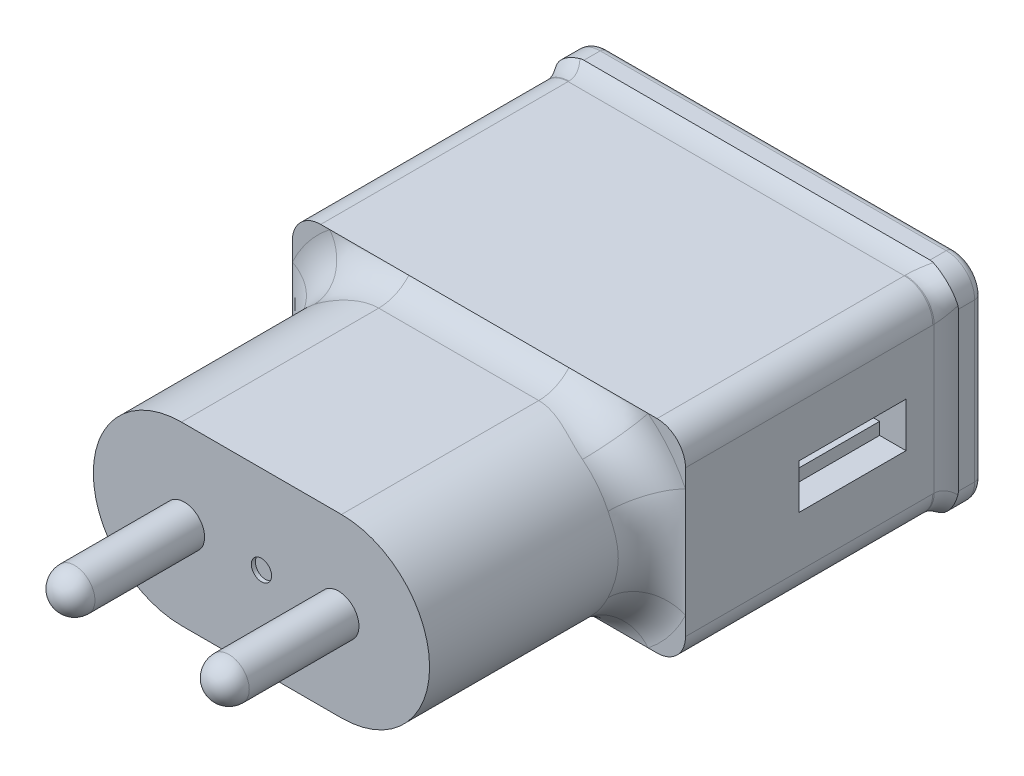
SolidWorks part; units mm, degrees
ref_plane "Front Plane" through (0, 0, 0) normal (0, 0, 1) x (1, 0, 0)
ref_plane "Top Plane" through (0, 0, 0) normal (0, 1, 0) x (1, 0, 0)
ref_plane "Right Plane" through (0, 0, 0) normal (1, 0, 0) x (0, 0, -1)
sketch "Sketch1" plane through (0, 0, 0) normal (0, 0, 1) x (1, 0, 0)
  line L0 (-9.85, 0) -> (9.85, 0) construction
  line L1 (-9.85, 10.85) -> (9.85, 10.85)
  line L2 (-9.85, -10.85) -> (9.85, -10.85)
  arc A0 (-9.85, 10.85) -> (-9.85, -10.85) centre (-9.85, 0) ccw
  arc A1 (9.85, -10.85) -> (9.85, 10.85) centre (9.85, 0) ccw
  point P2 (0, 0)
  point P8 (-20.7, 0)
  point P9 (20.7, 0)
  dimension "D1" = 41.4
  dimension "D2" = 21.7
extrude "Boss-Extrude1" add sketch "Sketch1" along normal mid plane 64
sketch "Sketch2" plane through (0, 0, -32) normal (0, 0, -1) x (-1, 0, 0)
  line L1 (-24.2, -12.5) -> (24.2, -12.5)
  line L2 (-24.2, -12.5) -> (-24.2, 12.5)
  line L3 (-24.2, 12.5) -> (24.2, 12.5)
  line L4 (24.2, -12.5) -> (24.2, 12.5)
  line L5 (-24.2, -12.5) -> (24.2, 12.5) construction
  line L6 (-24.2, 12.5) -> (24.2, -12.5) construction
  point P0 (0, 0)
  dimension "D1" = 25
  dimension "D2" = 48.4
extrude "Boss-Extrude2" add sketch "Sketch2" against normal blind 36
sketch "Sketch4" plane through (0, 0, -32) normal (0, 0, -1) x (-1, 0, 0)
  line L1 (-24.8, 13.2) -> (24.8, 13.2)
  line L2 (-24.8, 13.2) -> (-24.8, -13.2)
  line L3 (-24.8, -13.2) -> (24.8, -13.2)
  line L4 (24.8, 13.2) -> (24.8, -13.2)
  line L5 (-24.8, 13.2) -> (24.8, -13.2) construction
  line L6 (-24.8, -13.2) -> (24.8, 13.2) construction
  point P0 (0, 0)
  dimension "D1" = 49.6
  dimension "D2" = 26.4
extrude "Boss-Extrude3" add sketch "Sketch4" against normal blind 3
fillet "Fillet1" radius 5 2 edges at (20.7, 0, 4) (-20.7, 0, 4)
fillet "Fillet2" radius 5 4 edges at (24.2, 0, -29) (0, 12.5, -29) (-24.2, 0, -29) (0, -12.5, -29)
fillet "Fillet3" radius 1 4 edges at (0, -13.2, -32) (24.8, 0, -32) (0, 13.2, -32) (-24.8, 0, -32)
fillet "Fillet4" radius 3.5 12 edges at (-24.3731, 12.7243, -27.9292) (-24.2, 12.5008, -26.5368) (24.3963, 12.7509, -28.0124) (24.2, 12.5008, -26.5368) (24.3497, -12.6974, -27.8396) (24.2, -12.5008, -26.5368) (-24.3963, -12.7509, -28.0124) (-24.2, -12.5008, -26.5368) (-24.2, 12.5, -11.2243) (24.2, 12.5, -11.2243) (24.2, -12.5, -11.2243) (-24.2, -12.5, -11.2243)
sketch "Sketch5" plane through (0, 0, 32) normal (0, 0, 1) x (1, 0, 0)
  line L0 (-12, 0) -> (-12, -16.5784) construction
  circle A0 centre (-9.5, 0) radius 2.5
  dimension "D1" = 5
  dimension "D2" = 12
extrude "Boss-Extrude4" add sketch "Sketch5" along normal blind 16
fillet "Fillet5" radius 2.5 1 edges at (-7, 0, 48)
mirror "Mirror1" about plane through (0, 0, 0) normal (1, 0, 0) of "Fillet5", "Boss-Extrude4"
sketch "Sketch6" plane through (24.2, 0, 0) normal (1, 0, 0) x (0, 0, -1)
  line L0 (32, 12.2) -> (32, -12.2) construction
  line L1 (10, 2.75) -> (23.15, 2.75)
  line L2 (10, 2.75) -> (10, -2.75)
  line L3 (10, -2.75) -> (23.15, -2.75)
  line L4 (23.15, 2.75) -> (23.15, -2.75)
  line L5 (10, 2.75) -> (23.15, -2.75) construction
  line L6 (10, -2.75) -> (23.15, 2.75) construction
  point P0 (16.575, 0)
  dimension "D1" = 5.5
  dimension "D2" = 13.15
  dimension "D3" = 22
extrude "Cut-Extrude1" cut sketch "Sketch6" against normal blind 10
sketch "Sketch7" plane through (14.2, 0, 0) normal (1, 0, 0) x (0, 0, -1)
  line L0 (10, 2.75) -> (10, -2.75) construction
  line L1 (10.75, -0.5) -> (22.4, -0.5)
  line L2 (10.75, -0.5) -> (10.75, -2)
  line L3 (10.75, -2) -> (22.4, -2)
  line L4 (22.4, -0.5) -> (22.4, -2)
  line L5 (23.15, -2.75) -> (23.15, 2.75) construction
  line L6 (10, -2.75) -> (23.15, -2.75) construction
  point P6 (10.75, -1.25)
  dimension "D1" = 1.5
  dimension "D2" = 0.75
  dimension "D3" = 0.75
  dimension "D4" = 0.75
extrude "Boss-Extrude6" add sketch "Sketch7" along normal blind 7.5
sketch "Sketch8" plane through (0, 0, 32) normal (0, 0, 1) x (1, 0, 0)
  circle A0 centre (0, 0) radius 1.25
  dimension "D1" = 2.5
extrude "Cut-Extrude2" cut sketch "Sketch8" against normal blind 0.5
fillet "Fillet6" radius 3.5 2 edges at (-24.5071, -12.9071, -31.7071) (-24.8, -13.2, -30.4541)
fillet "Fillet7" radius 3.5 2 edges at (-24.5071, 12.9071, -31.7071) (-24.8, 13.2, -30.4541)
fillet "Fillet8" radius 3.5 2 edges at (24.5071, 12.9071, -31.7071) (24.8, 13.2, -30.4541)
fillet "Fillet9" radius 3.5 2 edges at (24.5071, -12.9071, -31.7071) (24.8, -13.2, -30.4541)
sketch "Sketch11" plane through (0, 0, -32) normal (0, 0, -1) x (-1, 0, 0)
  line L0 (8.0735, 1.7219) -> (7.4498, -1.4038)
  line L1 (7.4498, -1.4038) -> (6.0796, -1.4038)
  line L2 (6.0796, -1.4038) -> (5.4894, 1.7219)
  line L3 (5.4894, 1.7219) -> (6.3496, 1.7219)
  line L4 (6.3496, 1.7219) -> (6.7651, -1.1679)
  line L5 (6.7651, -1.1679) -> (7.2112, 1.7219)
  line L6 (7.2112, 1.7219) -> (8.0735, 1.7219)
  line L7 (9.3916, -0.5051) -> (9.3916, -0.754)
  line L8 (9.3916, -0.5051) -> (8.6464, -0.5051)
  line L9 (8.6464, -0.5051) -> (8.6464, -0.9474)
  line L10 (9.4189, -1.4911) -> (9.9751, -1.4911)
  line L11 (9.9751, 0.6903) -> (9.9751, 1.1473)
  line L12 (9.9751, 0.6903) -> (10.8379, 0.6903)
  line L13 (10.8379, 0.6903) -> (10.8379, 1.1473)
  line L14 (9.9751, 1.8277) -> (9.3119, 1.8277)
  line L15 (8.8945, 0.1805) -> (9.7597, -0.3338)
  line L16 (4.8742, 1.7219) -> (4.8742, -1.4038)
  line L17 (4.8742, -1.4038) -> (3.542, -1.4038)
  line L18 (3.542, -1.4038) -> (3.1337, 0.9721)
  line L19 (3.1337, 0.9721) -> (2.72, -1.4038)
  line L20 (2.72, -1.4038) -> (1.471, -1.4038)
  line L21 (1.471, -1.4038) -> (1.3993, 1.7219)
  line L22 (1.3993, 1.7219) -> (2.0955, 1.7219)
  line L23 (2.0955, 1.7219) -> (2.1606, -1.1139)
  line L24 (2.1606, -1.1139) -> (2.6544, 1.7219)
  line L25 (2.6544, 1.7219) -> (3.5415, 1.7219)
  line L26 (3.5415, 1.7219) -> (4.0288, -1.1139)
  line L27 (4.0288, -1.1139) -> (4.1042, 1.7219)
  line L28 (4.1042, 1.7219) -> (4.8742, 1.7219)
  line L29 (-0.8073, -0.5051) -> (-0.8073, -0.754)
  line L30 (-0.8073, -0.5051) -> (-1.5524, -0.5051)
  line L31 (-1.5524, -0.5051) -> (-1.5524, -0.9474)
  line L32 (-0.78, -1.4911) -> (-0.2238, -1.4911)
  line L33 (-0.2238, 0.6903) -> (-0.2238, 1.1473)
  line L34 (-0.2238, 0.6903) -> (0.639, 0.6903)
  line L35 (0.639, 0.6903) -> (0.639, 1.1473)
  line L36 (-0.2238, 1.8277) -> (-0.887, 1.8277)
  line L37 (-1.3043, 0.1805) -> (-0.4392, -0.3338)
  line L38 (-5.4357, -1.4281) -> (-5.4357, 1.6598)
  line L39 (-5.4357, 1.6598) -> (-6.164, 1.6598)
  line L40 (-6.164, 1.6598) -> (-6.164, -1.0343)
  line L41 (-6.164, -1.0343) -> (-6.9075, 1.6598)
  line L42 (-6.9075, 1.6598) -> (-8.0046, 1.6598)
  line L43 (-8.0046, 1.6598) -> (-8.0046, -1.3913)
  line L44 (-8.0046, -1.3913) -> (-7.2542, -1.3913)
  line L45 (-7.2542, -1.3913) -> (-7.2542, 1.1633)
  line L46 (-7.2542, 1.1633) -> (-6.5391, -1.4281)
  line L47 (-6.5391, -1.4281) -> (-5.4357, -1.4281)
  line L48 (-2.3622, -1.4038) -> (-3.1058, -1.4038)
  line L49 (-3.1058, -1.4038) -> (-3.1058, 0.9488)
  line L50 (-3.7418, 0.9488) -> (-3.7418, -1.4038)
  line L51 (-3.7418, -1.4038) -> (-4.5197, -1.4038)
  line L52 (-4.5197, -1.4038) -> (-4.5197, 1.0687)
  line L53 (-2.3622, -1.4038) -> (-2.3622, 1.1473)
  line L54 (-9.9984, 0) -> (-9.9984, 0.4272)
  line L55 (-9.9984, 0.4272) -> (-10.3188, 0.4272)
  line L56 (-10.3188, 0.4272) -> (-10.3188, 1.0687)
  line L57 (-9.9984, 0) -> (-11.0936, 0)
  line L58 (-11.0936, 0) -> (-11.0936, 1.0687)
  line L59 (-10.3188, -0.6925) -> (-10.3188, -0.4238)
  line L60 (-10.3188, -0.4238) -> (-11.0936, -0.4238)
  line L61 (-11.0936, -0.4238) -> (-11.0936, -0.754)
  line L62 (-8.8912, 1.2856) -> (-8.8912, -0.7431)
  line L63 (-9.6006, -1.4836) -> (-10.4001, -1.4836)
  line L64 (-9.6592, -0.7074) -> (-9.6592, 1.0296)
  arc A0 (-3.1058, 0.9488) -> (-3.7418, 0.9488) centre (-3.4238, 0.9488) ccw
  arc A1 (-2.3622, 1.1473) -> (-4.5197, 1.0687) centre (-3.4238, 0.637) ccw
  spline S0 degree 2 poles (8.6464, -0.9474) (8.8406, -1.4603) (9.4189, -1.4911) knots 0 0 0 1 1 1
  spline S1 degree 3 poles (9.9751, -1.4911) (10.2986, -1.5216) (10.8126, -1.1606) (10.8599, -0.302) (10.2923, 0.2869) (9.6616, 0.4352) (9.2185, 0.9192) (9.5016, 1.3768) (9.8598, 1.2698) (9.9751, 1.1473) knots 0 0 0 0 0.206801 0.362764 0.514217 0.708939 0.809724 0.881697 1 1 1 1
  spline S2 degree 2 poles (10.8379, 1.1473) (10.6397, 1.7829) (9.9751, 1.8277) knots 0 0 0 1 1 1
  spline S3 degree 3 poles (9.3119, 1.8277) (8.861, 1.7912) (8.4294, 1.1055) (8.6045, 0.3233) (8.8945, 0.1805) knots 0 0 0 0 0.574026 1 1 1 1
  spline S4 degree 3 poles (9.7597, -0.3338) (9.909, -0.4142) (10.0986, -0.7369) (9.8243, -1.0054) (9.5583, -0.9897) (9.3916, -0.8445) (9.3916, -0.754) knots 0 0 0 0 0.434555 0.577947 0.801581 1 1 1 1
  spline S5 degree 2 poles (-1.5524, -0.9474) (-1.3583, -1.4603) (-0.78, -1.4911) knots 0 0 0 1 1 1
  spline S6 degree 3 poles (-0.2238, -1.4911) (0.0997, -1.5216) (0.6138, -1.1606) (0.661, -0.302) (0.0934, 0.2869) (-0.5373, 0.4352) (-0.9803, 0.9192) (-0.6973, 1.3768) (-0.339, 1.2698) (-0.2238, 1.1473) knots 0 0 0 0 0.206801 0.362764 0.514217 0.708939 0.809724 0.881697 1 1 1 1
  spline S7 degree 2 poles (0.639, 1.1473) (0.4409, 1.7829) (-0.2238, 1.8277) knots 0 0 0 1 1 1
  spline S8 degree 3 poles (-0.887, 1.8277) (-1.3379, 1.7912) (-1.7694, 1.1055) (-1.5943, 0.3233) (-1.3043, 0.1805) knots 0 0 0 0 0.574026 1 1 1 1
  spline S9 degree 3 poles (-0.4392, -0.3338) (-0.2899, -0.4142) (-0.1003, -0.7369) (-0.3746, -1.0054) (-0.6405, -0.9897) (-0.8073, -0.8445) (-0.8073, -0.754) knots 0 0 0 0 0.434555 0.577947 0.801581 1 1 1 1
  spline S10 degree 2 poles (-11.0936, -0.754) (-11.0228, -1.3335) (-10.4001, -1.4836) knots 0 0 0 1 1 1
  spline S11 degree 3 poles (-11.0936, 1.0687) (-11.0238, 1.5398) (-10.075, 1.9505) (-9.184, 1.6985) (-8.8912, 1.2856) knots 0 0 0 0 0.480026 1 1 1 1
  spline S12 degree 3 poles (-8.8912, -0.7431) (-8.8912, -0.8921) (-9.0072, -1.1637) (-9.2466, -1.3272) (-9.5049, -1.4836) (-9.6006, -1.4836) knots 0 0 0 0 0.331371 0.700605 1 1 1 1
  spline S13 degree 2 poles (-10.3188, 1.0687) (-9.9912, 1.443) (-9.6592, 1.0296) knots 0 0 0 1 1 1
  spline S14 degree 2 poles (-10.3188, -0.6925) (-10.0029, -1.195) (-9.6592, -0.7074) knots 0 0 0 1 1 1
extrude "Cut-Extrude3" cut sketch "Sketch11" against normal blind 0.25
sketch "Sketch12" plane through (0, -12.5, 0) normal (0, -1, 0) x (1, 0, 0)
  line L0 (2.7677, -16.1544) -> (-15.3681, -16.1544) construction
  text T0 "Adaptive\r\nFast\r\nCharging" font "Arial Narrow" height in points 8
extrude "Cut-Extrude4" cut sketch "Sketch12" against normal blind 0.25
sketch "Sketch13" plane through (0, -12.5, 0) normal (0, -1, 0) x (1, 0, 0)
  line L0 (9.2922, -19.117) -> (5.7238, -19.117)
  line L1 (5.7238, -19.117) -> (7.508, -14.8952)
  line L2 (7.508, -14.8952) -> (4.8003, -14.8952)
  line L3 (4.8003, -14.8952) -> (10.422, -7.965)
  line L4 (10.422, -7.965) -> (7.6483, -14.1331)
  line L5 (7.6483, -14.1331) -> (10.422, -14.1331)
  line L6 (10.422, -14.1331) -> (9.2922, -19.117)
extrude "Cut-Extrude5" cut sketch "Sketch13" against normal blind 0.25
